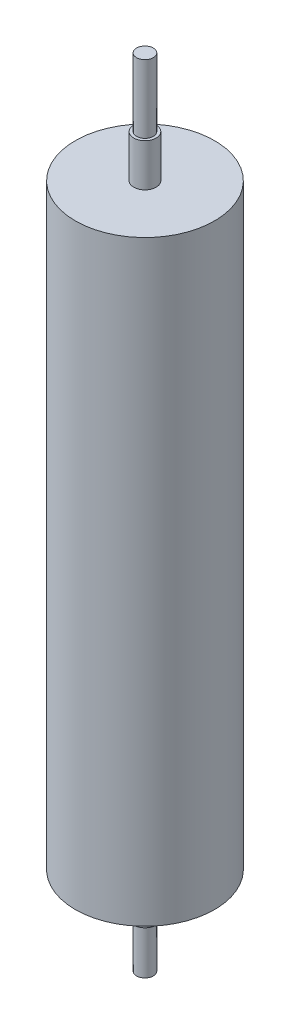
SolidWorks part; units mm, degrees
material "Stainless Steel (ferritic)"
ref_plane "Front Plane" through (0, 0, 0) normal (0, 0, 1) x (1, 0, 0)
ref_plane "Top Plane" through (0, 0, 0) normal (0, 1, 0) x (1, 0, 0)
ref_plane "Right Plane" through (0, 0, 0) normal (1, 0, 0) x (0, 0, -1)
sketch "Sketch1" plane through (0, 0, 0) normal (0, 1, 0) x (1, 0, 0)
  circle A0 centre (0, 0) radius 3.95
  circle A1 centre (0, 0) radius 3.45
  circle A2 centre (0, 0) radius 2.95
  circle A3 centre (0, 0) radius 24.5
  dimension "D1" = 7.9
  dimension "D2" = 6.9
  dimension "D3" = 5.9
  dimension "D4" = 49
extrude "Boss-Extrude8" add sketch "Sketch1" along normal blind 210 contours A3
extrude "Boss-Extrude9" add sketch "Sketch1<9>" against normal blind 15 contours A0
sketch "Sketch1<9>" plane through (0, 0, 0) normal (0, 1, 0) x (1, 0, 0) same geometry as "Sketch1"
extrude "Boss-Extrude10" add sketch "Sketch1<10>" against normal blind 16 from surface contours A2 region at (0, 0, 0) starting at face at (0, -15, 3.95)
sketch "Sketch1<10>" plane through (0, 0, 0) normal (0, 1, 0) x (1, 0, 0) same geometry as "Sketch1"
extrude "Boss-Extrude11" add sketch "Sketch1<11>" along normal blind 15 from surface contours A0 starting at face at (0, 210, 24.5)
sketch "Sketch1<11>" plane through (0, 0, 0) normal (0, 1, 0) x (1, 0, 0) same geometry as "Sketch1"
sketch "Sketch2" plane through (0, 225, 0) normal (0, 1, 0) x (1, 0, 0)
  circle A0 centre (0, 0) radius 2.95
  circle A1 centre (0, 0) radius 3.45
extrude "Boss-Extrude12" add sketch "Sketch2" along normal blind 24 contours A0 region at (0, 225, 0)
